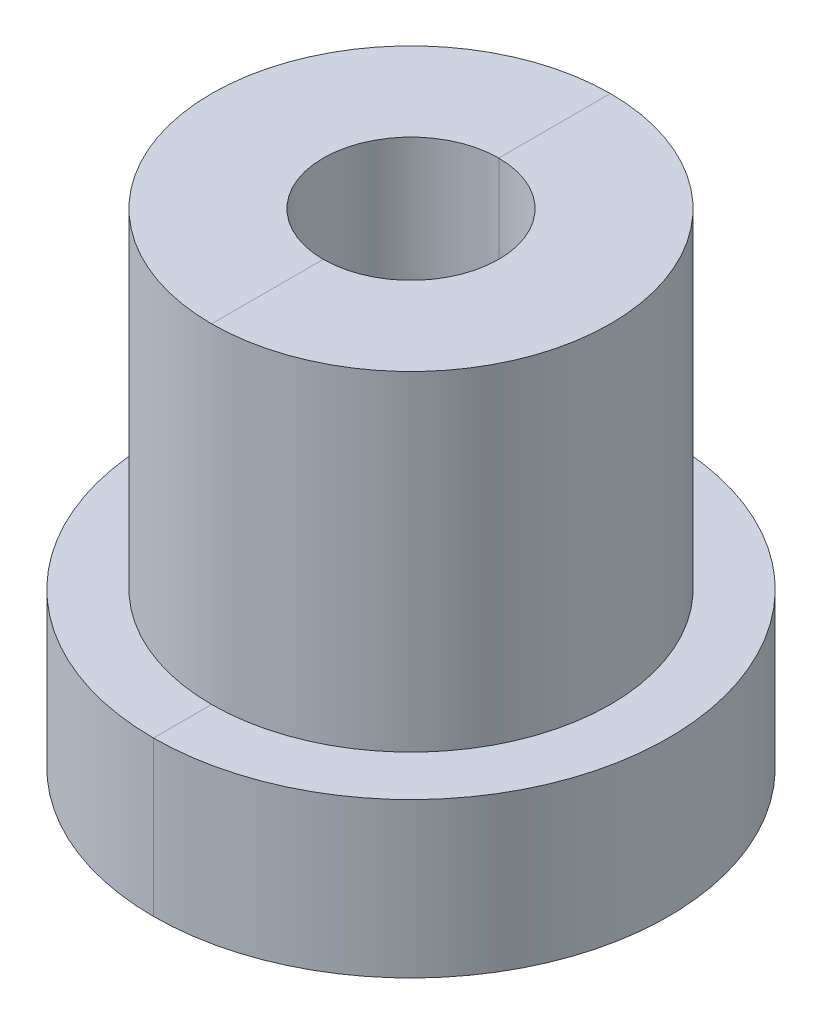
SolidWorks part; units mm, degrees
ref_plane "Front Plane" through (0, 0, 0) normal (0, 0, 1) x (1, 0, 0)
ref_plane "Top Plane" through (0, 0, 0) normal (0, 1, 0) x (1, 0, 0)
ref_plane "Right Plane" through (0, 0, 0) normal (1, 0, 0) x (0, 0, -1)
sketch "Sketch1" plane through (0, 0, 0) normal (0, 1, 0) x (1, 0, 0)
  circle A0 centre (0, 0) radius 7.9375
  dimension "D1" = 15.875
extrude "Boss-Extrude1" add sketch "Sketch1" along normal blind 4.7625
sketch "Sketch2" plane through (0, 4.7625, 0) normal (0, 1, 0) x (1, 0, 0)
  circle A0 centre (0, 0) radius 6.35
  dimension "D1" = 12.7
extrude "Boss-Extrude2" add sketch "Sketch2" along normal blind 10.16
sketch "Sketch4" plane through (0, 14.9225, 0) normal (0, 1, 0) x (1, 0, 0)
  circle A0 centre (0, 0) radius 6.1468
  circle A1 centre (0, 0) radius 6.35
  circle A2 centre (0, 0) radius 6.35
  dimension "D2" = 0.2032
  dimension "D1" = 0
extrude "Cut-Extrude2" cut sketch "Sketch4" against normal up to surface (10.16 mm away) up to face at (0, 4.7625, 6.35)
sketch "Sketch3" plane through (0, 14.9225, 0) normal (0, 1, 0) x (1, 0, 0)
  circle A0 centre (0, 0) radius 2.7051
  dimension "D1" = 5.4102
extrude "Cut-Extrude1" cut sketch "Sketch3" against normal through all
split line "Split Line1"
